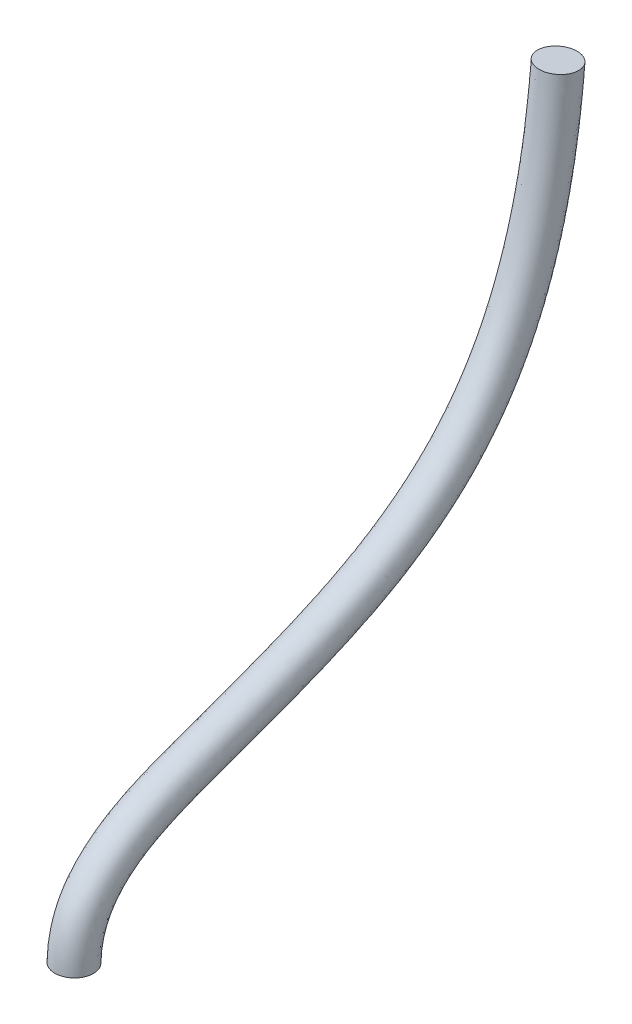
SolidWorks part; units mm, degrees
ref_plane "Front Plane" through (0, 0, 0) normal (0, 0, 1) x (1, 0, 0)
ref_plane "Top Plane" through (0, 0, 0) normal (0, 1, 0) x (1, 0, 0)
ref_plane "Right Plane" through (0, 0, 0) normal (1, 0, 0) x (0, 0, -1)
sketch "Sketch52" plane through (0, 0, 0) normal (1, 0, 0) x (0, 0, -1)
  spline S0 degree 3 poles (-42.3868, -8.3439) (-42.2577, -2.0864) (-18.8722, 6.4923) (-2.7323, 11.8872) (-0.4768, 38.3572) knots 0 0 0 0 0.247349 1 1 1 1
  dimension "D1" = 41.91
  dimension "D2" = 46.7011
sweep "Sweep2" add path "Sketch52" circular profile diameter 3.302 parameters "D3"=3.302
